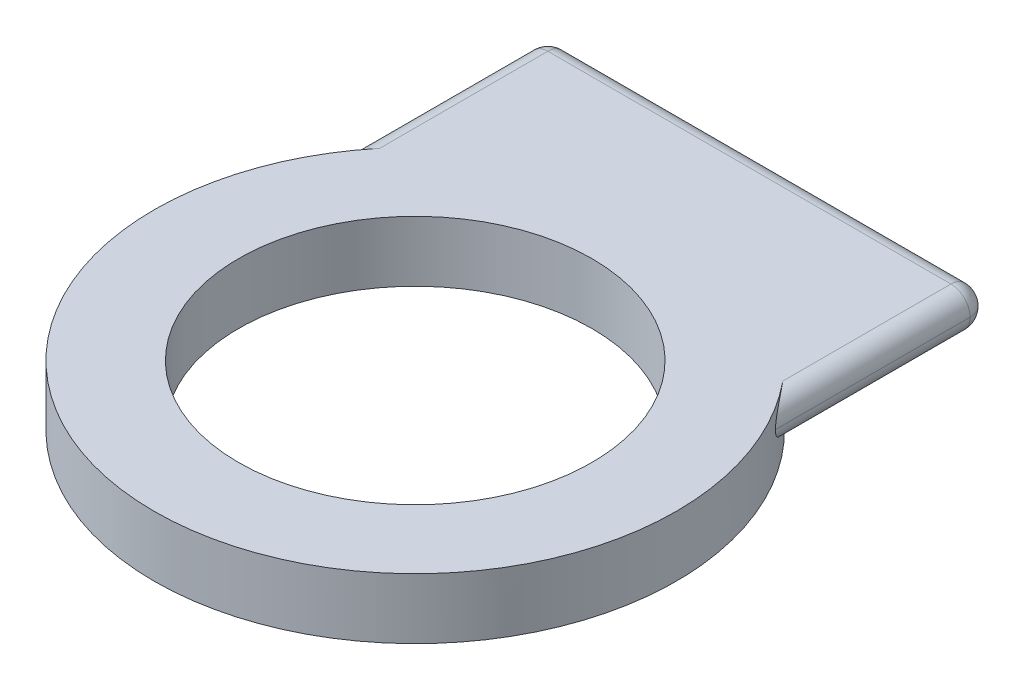
SolidWorks part; units mm, degrees
ref_plane "Front Plane" through (0, 0, 0) normal (0, 0, 1) x (1, 0, 0)
ref_plane "Top Plane" through (0, 0, 0) normal (0, 1, 0) x (1, 0, 0)
ref_plane "Right Plane" through (0, 0, 0) normal (1, 0, 0) x (0, 0, -1)
sketch "Sketch1" plane through (0, 0, 0) normal (0, 1, 0) x (1, 0, 0)
  line L1 (0, 0) -> (87.47, 0)
  line L2 (0, 0) -> (0, 70)
  line L3 (0, 70) -> (87.47, 70)
  line L4 (87.47, 0) -> (87.47, 70)
  dimension "D1" = 87.47
  dimension "D2" = 70
extrude "Boss-Extrude1" add sketch "Sketch1" along normal blind 7.6
sketch "Sketch2" plane through (0, 7.6, 0) normal (0, 1, 0) x (1, 0, 0)
  line L0 (0, 0) -> (87.47, 0) construction
  circle A0 centre (43.735, 0) radius 43.735
  dimension "D1" = 87.47
extrude "Boss-Extrude2" add sketch "Sketch2" against normal blind 12
sketch "Sketch3" plane through (0, 7.6, 0) normal (0, 1, 0) x (1, 0, 0)
  circle A0 centre (43.735, 0) radius 51.735
  arc A1 (0, 0) -> (87.47, 0) centre (43.735, 0) ccw construction
  dimension "D1" = 8
extrude "Boss-Extrude3" add sketch "Sketch3" against normal blind 12
sketch "Sketch4" plane through (0, 7.6, 0) normal (0, 1, 0) x (1, 0, 0)
  circle A0 centre (43.735, 0) radius 35
  dimension "D1" = 70
extrude "Cut-Extrude1" cut sketch "Sketch4" against normal blind 12
fillet "Fillet1" radius 3.8 4 edges at (87.47, 0, -48.8181) (87.47, 7.6, -48.8181) (0, 7.6, -48.8181) (0, 0, -48.8181)
fillet "Fillet2" radius 3.8 6 edges at (86.357, 6.487, -70) (86.357, 1.113, -70) (1.113, 1.113, -70) (1.113, 6.487, -70) (43.735, 0, -70) (43.735, 7.6, -70)
